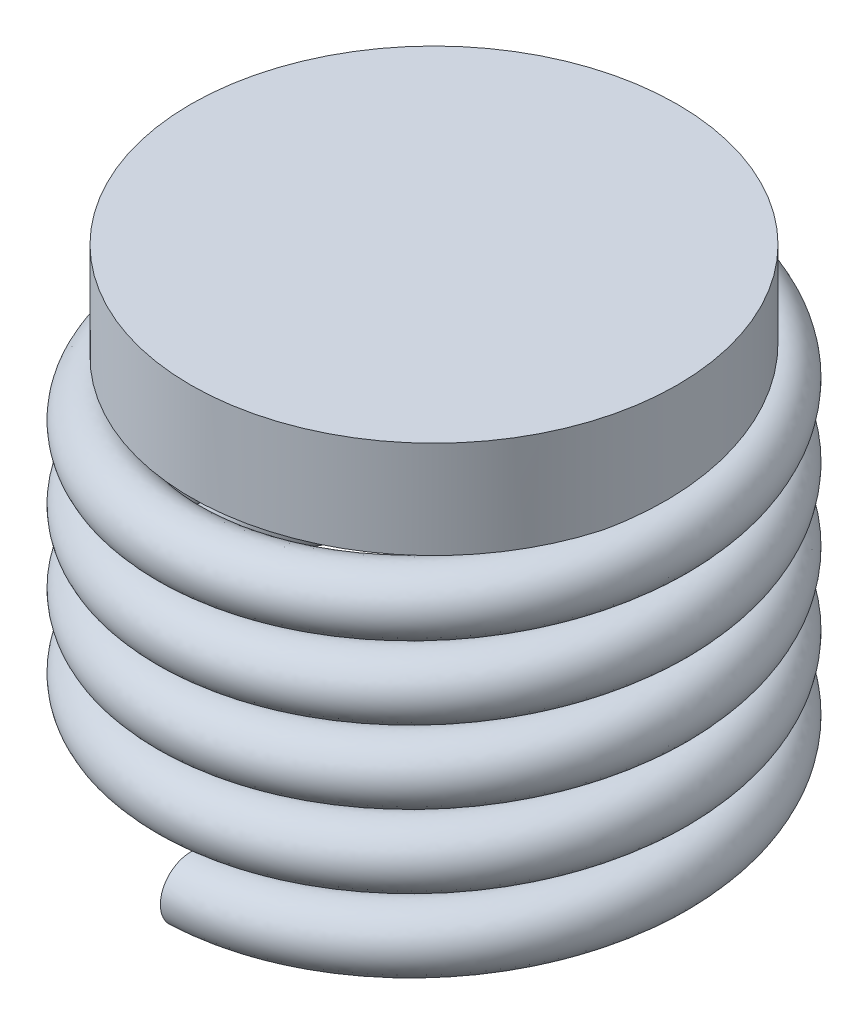
SolidWorks part; units mm, degrees
ref_plane "前视基准面" through (0, 0, 0) normal (0, 0, 1) x (1, 0, 0)
ref_plane "上视基准面" through (0, 0, 0) normal (0, 1, 0) x (1, 0, 0)
ref_plane "右视基准面" through (0, 0, 0) normal (1, 0, 0) x (0, 0, -1)
other "Configuration Table"
sketch "草图1" plane through (0, 0, 0) normal (0, 1, 0) x (1, 0, 0)
  circle A0 centre (0, 0) radius 10
  dimension "D1" = 20
extrude "凸台-拉伸1" add sketch "草图1" along normal blind 4
sketch "草图2" plane through (0, 0, 0) normal (0, 1, 0) x (1, 0, 0)
  circle A0 centre (0, 0) radius 10
  dimension "D1" = 20
curve "螺旋线/涡状线1" pitch 3 height 15 turns 5
sketch "草图4" plane through (0, 0, 0) normal (1, 0, 0) x (0, 0, -1)
  circle A0 centre (-9.9992, -13.8691) radius 1.25
  spline S0 degree 3 poles (7.0711, 0) (7.9907, -0.0621) (9.482, -0.1877) (10.2596, -0.375) (9.4795, -0.5625) (7.2551, -0.75) (3.9265, -0.9375) (0, -1.125) (-3.9265, -1.3125) (-7.2552, -1.5) (-9.4793, -1.6875) (-10.2603, -1.875) (-9.4793, -2.0625) (-7.2552, -2.25) (-2.8169, -2.5) (2.8169, -2.75) (7.2552, -3) (9.4793, -3.1875) (10.2603, -3.375) (9.4793, -3.5625) (7.2552, -3.75) (2.8169, -4) (-2.8169, -4.25) (-7.2552, -4.5) (-9.4793, -4.6875) (-10.2603, -4.875) (-9.4793, -5.0625) (-7.2552, -5.25) (-2.8169, -5.5) (2.8169, -5.75) (7.2552, -6) (9.4793, -6.1875) (10.2603, -6.375) (9.4793, -6.5625) (7.2552, -6.75) (2.8169, -7) (-2.8169, -7.25) (-7.2552, -7.5) (-9.4793, -7.6875) (-10.2603, -7.875) (-9.4793, -8.0625) (-7.2552, -8.25) (-2.8169, -8.5) (2.8169, -8.75) (7.2552, -9) (9.4793, -9.1875) (10.2603, -9.375) (9.4793, -9.5625) (7.2552, -9.75) (2.8169, -10) (-2.8169, -10.25) (-7.2552, -10.5) (-9.4793, -10.6875) (-10.2603, -10.875) (-9.4793, -11.0625) (-7.2552, -11.25) (-2.8169, -11.5) (2.8169, -11.75) (7.2552, -12) (9.4793, -12.1875) (10.2603, -12.375) (9.4793, -12.5625) (7.2552, -12.75) (2.8169, -13) (-2.8169, -13.25) (-7.2552, -13.5) (-9.4793, -13.6875) (-10.2603, -13.875) (-9.4793, -14.0625) (-7.2551, -14.25) (-3.9267, -14.4375) (0.0007, -14.625) (3.9238, -14.8123) (6.1514, -14.9379) (7.0711, -15) knots 0 0 0 0 0.0125 0.025 0.0375 0.05 0.0625 0.075 0.0875 0.1 0.1125 0.125 0.1375 0.15 0.1625 0.1875 0.2 0.2125 0.225 0.2375 0.25 0.2625 0.2875 0.3 0.3125 0.325 0.3375 0.35 0.3625 0.3875 0.4 0.4125 0.425 0.4375 0.45 0.4625 0.4875 0.5 0.5125 0.525 0.5375 0.55 0.5625 0.5875 0.6 0.6125 0.625 0.6375 0.65 0.6625 0.6875 0.7 0.7125 0.725 0.7375 0.75 0.7625 0.7875 0.8 0.8125 0.825 0.8375 0.85 0.8625 0.8875 0.9 0.9125 0.925 0.9375 0.95 0.9625 0.975 0.9875 1 1 1 1 construction
  dimension "D1" = 2.5
  dimension "D2" = 9.9992
sweep "扫描1" add profiles "草图4" path "螺旋线/涡状线1"
